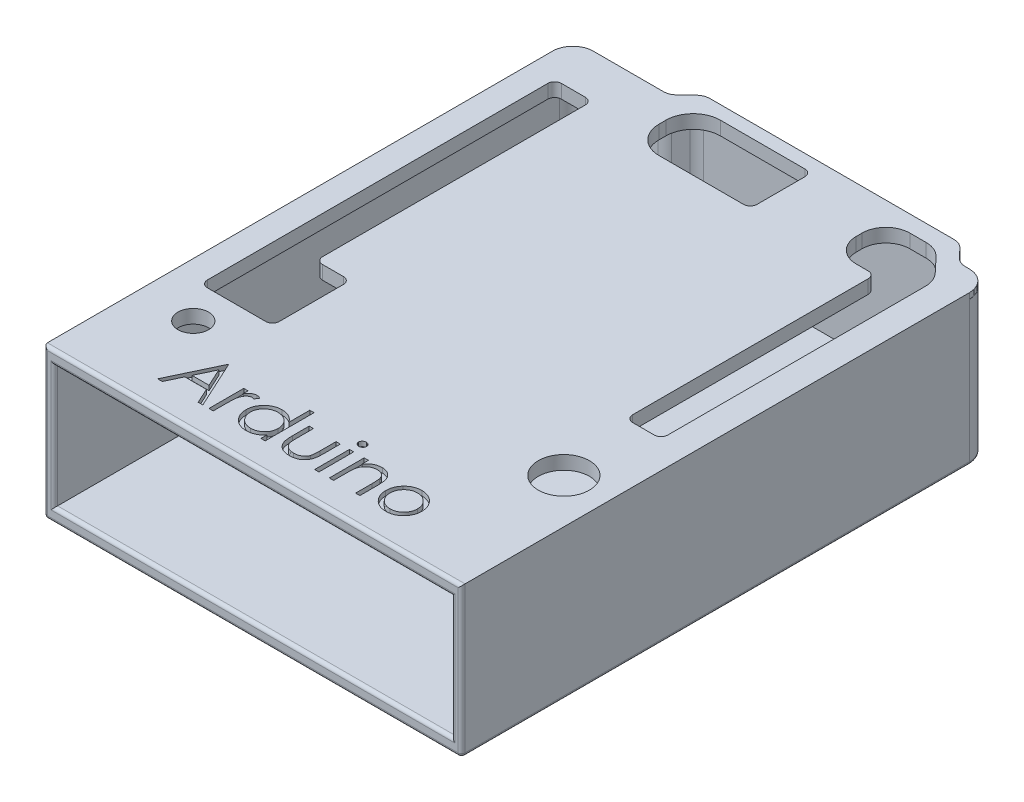
SolidWorks part; units mm, degrees
material "Glass"
ref_plane "Front Plane" through (0, 0, 0) normal (0, 0, 1) x (1, 0, 0)
ref_plane "Top Plane" through (0, 0, 0) normal (0, 1, 0) x (1, 0, 0)
ref_plane "Right Plane" through (0, 0, 0) normal (1, 0, 0) x (0, 0, -1)
sketch "Sketch1" plane through (0, 0, 0) normal (0, 1, 0) x (1, 0, 0)
  line L1 (-35, 50) -> (35, 50)
  line L2 (-35, 50) -> (-35, -50)
  line L3 (-35, -50) -> (35, -50)
  line L4 (35, 50) -> (35, -50)
  line L5 (-35, 50) -> (35, -50) construction
  line L6 (-35, -50) -> (35, 50) construction
  point P0 (0, 0)
  dimension "D1" = 70
  dimension "D2" = 100
extrude "Boss-Extrude1" add sketch "Sketch1" along normal blind 2
sketch "Sketch2" plane through (0, 2, 0) normal (0, 1, 0) x (1, 0, 0)
  line L0 (-33.0726, 52.8811) -> (-33.0726, -56.2729)
  line L1 (-33.0726, -56.2729) -> (-47.795, -51.6582)
  line L2 (-47.795, -51.6582) -> (-45.7843, 52.8811)
  line L3 (-45.7843, 52.8811) -> (-33.0726, 52.8811)
  line L4 (-30.5726, 39.4121) -> (-30.5726, -26.6279) construction
  dimension "D1" = 2.5
extrude "Cut-Extrude1" cut sketch "Sketch2" against normal blind 10
sketch "Sketch3" plane through (0, 2, 0) normal (0, 1, 0) x (1, 0, 0)
  line L0 (-41.9394, 44.4521) -> (53.7814, 44.4521)
  line L1 (53.7814, 44.4521) -> (53.7814, 57.2998)
  line L2 (53.7814, 57.2998) -> (-41.9394, 57.2998)
  line L3 (-41.9394, 57.2998) -> (-41.9394, 44.4521)
  line L4 (17.6874, 41.9521) -> (-15.0786, 41.9521) construction
  dimension "D1" = 2.5
extrude "Cut-Extrude2" cut sketch "Sketch3" against normal blind 10
sketch "Sketch4" plane through (0, 2, 0) normal (0, 1, 0) x (1, 0, 0)
  line L0 (25.2674, 48.3702) -> (25.2674, -29.1279)
  line L1 (25.2674, -29.1279) -> (-38.6238, -29.1279)
  line L2 (-38.6238, -29.1279) -> (-38.6238, -57.7653)
  line L3 (-38.6238, -57.7653) -> (46.0746, -57.7653)
  line L4 (46.0746, -57.7653) -> (46.0746, 51.6787)
  line L5 (46.0746, 51.6787) -> (25.2674, 51.6787)
  line L6 (25.2674, 51.6787) -> (25.2674, 48.3702)
  line L7 (22.7674, -26.6279) -> (22.7674, 39.4121) construction
  line L8 (-30.5726, -26.6279) -> (22.7674, -26.6279) construction
  dimension "D1" = 2.5
  dimension "D2" = 2.5
extrude "Cut-Extrude3" cut sketch "Sketch4" against normal blind 10
sketch "Sketch5" plane through (0, 2, 0) normal (0, 1, 0) x (1, 0, 0)
  circle A0 centre (-12.7926, 39.4121) radius 2.0009
  circle A1 centre (15.1474, 39.4121) radius 2.0009
  circle A2 centre (-28.0326, -11.3879) radius 2.0009
  circle A3 centre (20.2274, -12.6579) radius 2.0009
  dimension "D1" = 4.0019
extrude "Cut-Extrude4" cut sketch "Sketch5" against normal blind 10
sketch "Sketch6" plane through (0, 0, 0) normal (0, 1, 0) x (1, 0, 0)
  circle A0 centre (-12.7926, 39.4121) radius 2.0009
  circle A1 centre (-12.7926, 39.4121) radius 2.75
  circle A2 centre (15.1474, 39.4121) radius 2.0009
  circle A3 centre (15.1474, 39.4121) radius 2.75
  circle A4 centre (20.2274, -12.6579) radius 2.0009
  circle A5 centre (20.2274, -12.6579) radius 2.75
  circle A6 centre (-28.0326, -11.3879) radius 2.0009
  circle A7 centre (-28.0326, -11.3879) radius 2.75
  dimension "D1" = 5.5
  dimension "D2" = 5.5
  dimension "D3" = 5.5
  dimension "D4" = 5.5
extrude "Boss-Extrude2" add sketch "Sketch6" along normal blind 4.5
sketch "Sketch7" plane through (22.7674, 6.15, 26.6279) normal (0, 1, 0) x (1, 0, 0)
  line L0 (-55.84, 71.08) -> (2.5, 71.08)
  line L1 (2.5, 71.08) -> (2.5, 72.58)
  line L2 (2.5, 72.58) -> (-55.84, 72.58)
  line L3 (-55.84, 72.58) -> (-55.84, 71.08)
  dimension "D1" = 1.5
extrude "Boss-Extrude3" add sketch "Sketch7" along normal blind 15 and the other way blind 6.5 separate body
sketch "Sketch8" plane through (0, 0, 0) normal (0, 1, 0) x (1, 0, 0)
  line L0 (-33.0726, 45.9521) -> (-34.5726, 45.9521)
  line L1 (-34.5726, 45.9521) -> (-34.5726, -29.1279)
  line L2 (-34.5726, -29.1279) -> (-33.0726, -29.1279)
  line L3 (-33.0726, -29.1279) -> (-33.0726, 45.9521)
  line L4 (25.2674, 45.9521) -> (26.7674, 45.9521)
  line L5 (26.7674, 45.9521) -> (26.7674, -29.1279)
  line L6 (26.7674, -29.1279) -> (25.2674, -29.1279)
  line L7 (25.2674, -29.1279) -> (25.2674, 45.9521)
  dimension "D1" = 1.5
  dimension "D2" = 1.5
extrude "Boss-Extrude4" add sketch "Sketch8" along normal blind 22
sketch "Sketch9" plane through (0, 0, 0) normal (1, 0, 0) x (0, 0, -1)
  line L0 (-29.1279, 0) -> (47.696, 0)
  line L1 (47.696, 0) -> (47.696, -7.0784)
  line L2 (47.696, -7.0784) -> (-35.9897, -7.0784)
  line L3 (-35.9897, -7.0784) -> (-35.9897, 0)
  line L4 (-35.9897, 0) -> (-29.1279, 0)
  line L5 (45.9521, 21.15) -> (-38.244, 21.15)
  line L6 (-38.244, 21.15) -> (-38.244, 38.4712)
  line L7 (-38.244, 38.4712) -> (45.9521, 38.4712)
  line L8 (45.9521, 38.4712) -> (45.9521, 21.15)
extrude "Cut-Extrude5" cut sketch "Sketch9" against normal blind 62 and the other way blind 42
fillet "Fillet1" radius 3 2 edges at (-34.5726, 10.575, -45.9521) (26.7674, 10.575, -45.9521)
sketch "Sketch10" plane through (0, 0, 0) normal (0, 1, 0) x (1, 0, 0)
  line L0 (-36.4242, 41.9121) -> (-19.7703, 41.9121)
  line L1 (-19.7703, 41.9121) -> (-13.4344, 48.248)
  line L2 (-13.4344, 48.248) -> (-36.4242, 48.248)
  line L3 (-36.4242, 48.248) -> (-36.4242, 41.9121)
  line L4 (-15.0786, 41.9521) -> (-17.6186, 39.4121) construction
  line L5 (-17.6186, 39.4121) -> (-30.5726, 39.4121) construction
  dimension "D1" = 2.5
extrude "Cut-Extrude7" cut sketch "Sketch10" along normal blind 62
sketch "Sketch11" plane through (0, 0, 0) normal (0, 1, 0) x (1, 0, 0)
  line L0 (15.5106, 47.6645) -> (21.3451, 41.83)
  line L1 (21.3451, 41.83) -> (28.5317, 41.83)
  line L2 (28.5317, 41.83) -> (28.5317, 49.4862)
  line L3 (28.5317, 49.4862) -> (15.5106, 47.6645)
  line L4 (20.2274, 39.4121) -> (17.6874, 41.9521) construction
  line L5 (22.7674, 39.4121) -> (20.2274, 39.4121) construction
  dimension "D1" = 2.5
extrude "Cut-Extrude8" cut sketch "Sketch11" along normal blind 62
sketch "Sketch12" plane through (0, 0, 0) normal (0, 1, 0) x (1, 0, 0)
  line L0 (-34.5726, -27.0521) -> (26.7674, -27.0521)
  line L1 (-34.5726, 41.9121) -> (-34.5726, -29.1279) construction
  line L2 (26.7674, -29.1279) -> (26.7674, 41.83) construction
  line L3 (26.7674, -27.0521) -> (26.7674, -34.2683)
  line L4 (26.7674, -34.2683) -> (-34.5726, -34.2683)
  line L5 (-34.5726, -34.2683) -> (-34.5726, -27.0521)
extrude "Boss-Extrude5" add sketch "Sketch12" along normal blind 2
sketch "Sketch13" plane through (0, 0, 0) normal (0, 1, 0) x (1, 0, 0)
  line L0 (-33.0726, -29.1279) -> (-33.0726, -34.2683)
  line L1 (-34.5726, -34.2683) -> (26.7674, -34.2683) construction
  line L2 (-33.0726, -34.2683) -> (-34.5726, -34.2683)
  line L3 (-34.5726, -34.2683) -> (-34.5726, -29.1279)
  line L4 (-34.5726, -29.1279) -> (-33.0726, -29.1279)
  line L5 (25.2674, -29.1279) -> (25.2674, -34.2683)
  line L6 (25.2674, -34.2683) -> (26.7674, -34.2683)
  line L7 (26.7674, -34.2683) -> (26.7674, -29.1279)
  line L8 (26.7674, -29.1279) -> (25.2674, -29.1279)
extrude "Boss-Extrude6" add sketch "Sketch13" along normal blind 22
sketch "Sketch14" plane through (0, 0, 0) normal (0, 1, 0) x (1, 0, 0)
  line L0 (-34.5726, 41.9121) -> (-19.7703, 41.9121)
  line L1 (-19.7703, 41.9121) -> (-15.7303, 45.9521)
  line L2 (-15.7303, 45.9521) -> (-17.8516, 45.9521)
  line L3 (-17.8516, 45.9521) -> (-20.3916, 43.4121)
  line L4 (-20.3916, 43.4121) -> (-34.5726, 43.4121)
  line L5 (-34.5726, 43.4121) -> (-34.5726, 41.9121)
  dimension "D1" = 1.5
  dimension "D2" = 1.5
extrude "Boss-Extrude7" add sketch "Sketch14" along normal blind 22
sketch "Sketch15" plane through (0, 2, 0) normal (0, 1, 0) x (1, 0, 0)
  line L0 (17.2229, 45.9521) -> (19.7618, 45.9521)
  line L1 (19.7618, 45.9521) -> (22.2501, 43.33)
  line L2 (22.2501, 43.33) -> (26.7674, 43.33)
  line L3 (26.7674, 43.33) -> (26.7674, 41.83)
  line L4 (26.7674, 41.83) -> (21.3451, 41.83)
  line L5 (21.3451, 41.83) -> (17.2229, 45.9521)
  dimension "D1" = 1.5
  dimension "D2" = 1.5
extrude "Boss-Extrude9" add sketch "Sketch15" along normal blind 32 and the other way blind 2
sketch "Sketch16" plane through (0, 0, 0) normal (1, 0, 0) x (0, 0, -1)
  line L0 (-28.0382, 21.15) -> (-36.9454, 21.15)
  line L1 (-29.1279, 21.15) -> (41.83, 21.15) construction
  line L2 (-36.9454, 21.15) -> (-36.9454, 45.772)
  line L3 (-36.9454, 45.772) -> (52.0185, 45.772)
  line L4 (52.0185, 45.772) -> (52.0185, 21.15)
  line L5 (52.0185, 21.15) -> (-28.0382, 21.15)
extrude "Cut-Extrude9" cut sketch "Sketch16" against normal blind 42 and the other way blind 32
fillet "Fillet2" radius 3 2 edges at (26.7674, 10.575, -43.33) (-34.5726, 10.575, -43.4121)
fillet "Fillet3" radius 2 9 edges at (25.2674, 11.575, -41.83) (21.3451, 11.575, -41.83) (22.2501, 10.575, -43.33) (19.7618, 10.575, -45.9521) (-17.8516, 10.575, -45.9521) (-17.2303, 11.575, -44.4521) (-33.0726, 11.575, -41.9121) (-19.7703, 11.575, -41.9121) (-20.3916, 10.575, -43.4121)
sketch "Sketch17" plane through (0, 0, 0) normal (0, 1, 0) x (1, 0, 0)
  line L0 (-34.5726, -34.2683) -> (-34.5726, 40.4121)
  line L1 (-21.22, 43.4121) -> (-31.5726, 43.4121) construction
  line L2 (-31.5726, 43.4121) -> (-21.22, 43.4121)
  line L3 (-21.22, 43.4121) -> (-20.7019, 43.4804)
  line L4 (-20.7019, 43.4804) -> (-20.22, 43.6801)
  line L5 (-20.22, 43.6801) -> (-18.4374, 45.3664)
  line L6 (-18.4374, 45.3664) -> (-18.0235, 45.684)
  line L7 (-18.0235, 45.684) -> (-17.541, 45.884)
  line L8 (-17.541, 45.884) -> (-17.0232, 45.9521)
  line L9 (-17.0232, 45.9521) -> (18.9025, 45.9521)
  line L10 (18.9025, 45.9521) -> (19.3076, 45.9107)
  line L11 (19.3076, 45.9107) -> (19.692, 45.7897)
  line L12 (19.692, 45.7897) -> (20.0503, 45.59)
  line L13 (20.0503, 45.59) -> (20.3533, 45.3289)
  line L14 (20.3533, 45.3289) -> (21.6586, 43.9533)
  line L15 (21.6586, 43.9533) -> (21.9641, 43.6904)
  line L16 (21.9641, 43.6904) -> (22.3199, 43.4924)
  line L17 (22.3199, 43.4924) -> (22.7065, 43.371)
  line L18 (22.7065, 43.371) -> (23.1094, 43.33)
  line L19 (23.1094, 43.33) -> (23.7674, 43.33)
  line L20 (23.7674, 43.33) -> (24.5448, 43.2275)
  line L21 (24.5448, 43.2275) -> (25.2674, 42.928)
  line L22 (25.2674, 42.928) -> (25.8887, 42.4513)
  line L23 (25.8887, 42.4513) -> (26.3652, 41.8304)
  line L24 (26.3652, 41.8304) -> (26.6651, 41.1067)
  line L25 (26.6651, 41.1067) -> (26.7674, 40.33)
  line L26 (26.7674, 40.33) -> (26.7674, -34.2683)
  line L27 (26.7674, -34.2683) -> (-34.5726, -34.2683)
  arc A0 (-34.5726, 40.4121) -> (-31.5726, 43.4121) centre (-31.5726, 40.4121) cw
  arc A1 (-21.22, 43.4121) -> (-19.8058, 43.9979) centre (-21.22, 45.4121) ccw construction
  arc A2 (-17.0232, 45.9521) -> (-18.4374, 45.3664) centre (-17.0232, 43.9521) ccw construction
  arc A3 (20.3533, 45.3289) -> (18.9025, 45.9521) centre (18.9025, 43.9521) ccw construction
  arc A4 (21.6586, 43.9533) -> (23.1094, 43.33) centre (23.1094, 45.33) ccw construction
  arc A5 (26.7674, 40.33) -> (23.7674, 43.33) centre (23.7674, 40.33) ccw construction
extrude "Boss-Extrude10" add sketch "Sketch17" along normal blind 2 from offset 20
fillet "Fillet5" radius 0.5 21 edges at (-34.5726, 0, -3.0719) (-33.6939, 0, -42.5335) (-26.3963, 0, -43.4121) (-20.4546, 0, -43.5644) (-19.1216, 0, -44.6821) (-17.7885, 0, -45.7999) (0.9397, 0, -45.9521) (19.692, 0, -45.7897) (21.0059, 0, -44.6411) (22.3199, 0, -43.4924) (23.4384, 0, -43.33) (25.8887, 0, -42.4513) (26.7674, 0, -3.0308) (-3.9026, 0, 34.2683) (25.2674, 11, 34.2683) (-3.9026, 2, 34.2683) (-33.0726, 11, 34.2683) (-3.9026, 20, 34.2683) (26.7674, 11, 34.2683) (-34.5726, 11, 34.2683) (-3.9026, 22, 34.2683)
sketch "Sketch18" plane through (0, 0, 0) normal (0, 1, 0) x (1, 0, 0)
  line L0 (-29.8106, 36.9665) -> (-26.3106, 36.9665)
  line L1 (-25.3106, 35.9665) -> (-25.3106, -2.6089)
  line L2 (-25.3106, -15.0335) -> (-29.8106, -15.0335)
  line L3 (-30.8106, -14.0335) -> (-30.8106, 35.9665)
  line L4 (-25.3106, -15.0335) -> (-21.2456, -15.0335)
  line L5 (-20.2456, -14.0335) -> (-20.2456, -4.6089)
  line L6 (-21.2456, -3.6089) -> (-24.3106, -3.6089)
  arc A0 (-29.8106, -15.0335) -> (-30.8106, -14.0335) centre (-29.8106, -14.0335) cw
  arc A1 (-21.2456, -15.0335) -> (-20.2456, -14.0335) centre (-21.2456, -14.0335) ccw
  arc A2 (-20.2456, -4.6089) -> (-21.2456, -3.6089) centre (-21.2456, -4.6089) ccw
  arc A3 (-24.3106, -3.6089) -> (-25.3106, -2.6089) centre (-24.3106, -2.6089) cw
  arc A4 (-26.3106, 36.9665) -> (-25.3106, 35.9665) centre (-26.3106, 35.9665) cw
  arc A5 (-29.8106, 36.9665) -> (-30.8106, 35.9665) centre (-29.8106, 35.9665) ccw
  point P17 (-25.3106, 36.9665)
  point P20 (-30.8106, 36.9665)
  dimension "D3" = 1
  dimension "D1" = 5.5
  dimension "D2" = 52
extrude "Cut-Extrude10" cut sketch "Sketch18" against normal blind 15 from offset 30
sketch "Sketch19" plane through (0, 0, 0) normal (0, 1, 0) x (1, 0, 0)
  line L0 (-17.4641, 39.9656) -> (-17.4641, 38.9539)
  line L1 (-13.4641, 34.9539) -> (-1.0584, 34.9539)
  line L2 (-0.0584, 35.9539) -> (-0.0584, 42.9656)
  line L3 (-1.0584, 43.9656) -> (-13.4641, 43.9656)
  arc A1 (-1.0584, 34.9539) -> (-0.0584, 35.9539) centre (-1.0584, 35.9539) ccw
  arc A2 (-0.0584, 42.9656) -> (-1.0584, 43.9656) centre (-1.0584, 42.9656) ccw
  arc A4 (-13.4641, 34.9539) -> (-17.4641, 38.9539) centre (-13.4641, 38.9539) cw
  arc A5 (-17.4641, 39.9656) -> (-13.4641, 43.9656) centre (-13.4641, 39.9656) cw
  dimension "D2" = 4
extrude "Cut-Extrude11" cut sketch "Sketch19" against normal blind 15 from offset 30
sketch "Sketch20" plane through (0, 22, 0) normal (0, 1, 0) x (1, 0, 0)
  line L1 (22.7262, 37.8829) -> (22.7262, 0.0597)
  line L2 (21.7262, -0.9403) -> (18.5622, -0.9403)
  line L3 (17.5622, 0.0597) -> (17.5622, 34.645)
  line L4 (16.5622, 35.645) -> (14.8021, 35.645)
  line L5 (11.3021, 39.145) -> (11.3021, 40.0191)
  line L6 (14.8021, 43.5191) -> (17.2138, 43.5191)
  line L7 (19.7614, 42.419) -> (21.7738, 40.2829)
  arc A0 (22.7262, 0.0597) -> (21.7262, -0.9403) centre (21.7262, 0.0597) cw
  arc A1 (18.5622, -0.9403) -> (17.5622, 0.0597) centre (18.5622, 0.0597) cw
  arc A5 (16.5622, 35.645) -> (17.5622, 34.645) centre (16.5622, 34.645) cw
  arc A8 (14.8021, 35.645) -> (11.3021, 39.145) centre (14.8021, 39.145) cw
  arc A9 (11.3021, 40.0191) -> (14.8021, 43.5191) centre (14.8021, 40.0191) cw
  arc A10 (22.7262, 37.8829) -> (21.7738, 40.2829) centre (19.2262, 37.8829) ccw
  arc A11 (19.7614, 42.419) -> (17.2138, 43.5191) centre (17.2138, 40.0191) ccw
  dimension "D1" = 1
  dimension "D3" = 3.5
  dimension "D4" = 3.5
extrude "Cut-Extrude12" cut sketch "Sketch20" against normal blind 5
sketch "Sketch21" plane through (0, 0, 0) normal (0, 1, 0) x (1, 0, 0)
  line L0 (-29.5898, -17.266) -> (-23.4816, -23.3741) construction
  circle A0 centre (-26.6356, -20.2779) radius 2.2489
extrude "Cut-Extrude13" cut sketch "Sketch21" against normal blind 15 from offset 30
sketch "Sketch23" plane through (0, 22, 0) normal (0, 1, 0) x (1, 0, 0)
  text T0 "Arduino " font "Century Gothic" height 7
extrude "Cut-Extrude15" cut sketch "Sketch23" against normal blind 0.7
sketch "Sketch24" plane through (0, 22, 0) normal (0, 1, 0) x (1, 0, 0)
  circle A0 centre (20.2262, -12.7124) radius 3.7546
extrude "Cut-Extrude16" cut sketch "Sketch24" against normal blind 10.7
